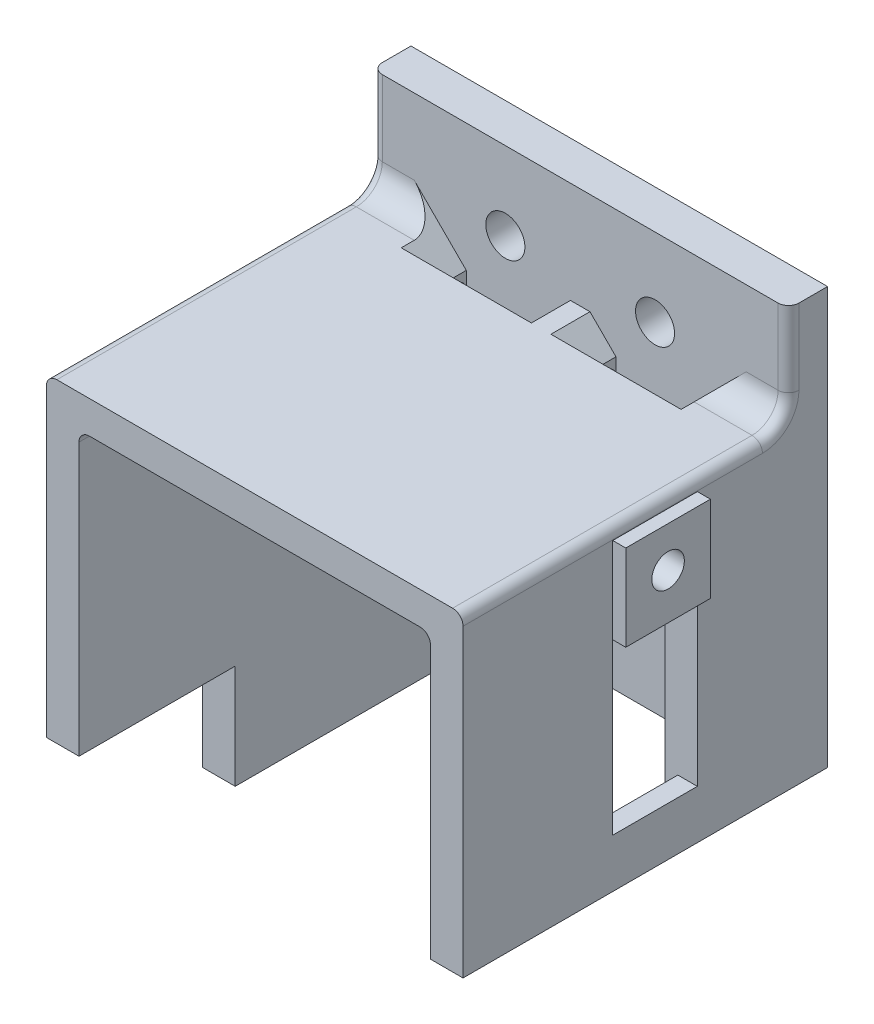
SolidWorks part; units mm, degrees
ref_plane "Płaszczyzna przednia" through (0, 0, 0) normal (0, 0, 1) x (1, 0, 0)
ref_plane "Płaszczyzna górna" through (0, 0, 0) normal (0, 1, 0) x (1, 0, 0)
ref_plane "Płaszczyzna prawa" through (0, 0, 0) normal (1, 0, 0) x (0, 0, -1)
sketch "Szkic1" plane through (0, 0, 0) normal (0, 0, 1) x (1, 0, 0)
  line L0 (-5.75, 3.4578) -> (5.75, 3.4578) construction
  line L2 (-16, 9.4578) -> (16, 9.4578)
  line L3 (-16, 9.4578) -> (-16, -2.5422)
  line L4 (-16, -2.5422) -> (16, -2.5422)
  line L5 (16, 9.4578) -> (16, -2.5422)
  line L6 (-16, 9.4578) -> (16, -2.5422) construction
  line L7 (-16, -2.5422) -> (16, 9.4578) construction
  circle A0 centre (-5.75, 3.4578) radius 1.5
  circle A1 centre (5.75, 3.4578) radius 1.5
  point P4 (0, 3.4578)
  point P10 (0, -2.5422)
  dimension "D1" = 3
  dimension "D2" = 3
  dimension "D3" = 5.75
  dimension "D4" = 5.75
  dimension "D5" = 32
  dimension "D6" = 6
extrude "Dodanie-wyciągnięcie1" add sketch "Szkic1" along normal blind 3
sketch "Szkic6" plane through (0, -2.5422, 0) normal (0, -1, 0) x (1, 0, 0)
  line L1 (-16, 3) -> (16, 3)
  line L2 (-16, 3) -> (-16, 0)
  line L3 (-16, 0) -> (16, 0)
  line L4 (16, 3) -> (16, 0)
extrude "Dodanie-wyciągnięcie3" add sketch "Szkic6" along normal blind 20
sketch "Szkic7" plane through (0, 0, 3) normal (0, 0, 1) x (1, 0, 0)
  line L0 (-16, 9.4578) -> (-16, -22.5422) construction
  line L1 (-16, -0.8422) -> (16, -0.8422)
  line L2 (-16, -0.8422) -> (-16, 1.6578)
  line L3 (-16, 1.6578) -> (16, 1.6578)
  line L4 (16, -0.8422) -> (16, 1.6578)
  line L5 (16, -22.5422) -> (16, 9.4578) construction
  line L6 (16, 9.4578) -> (-16, 9.4578) construction
  dimension "D1" = 2.5
  dimension "D2" = 10.3
extrude "Dodanie-wyciągnięcie4" add sketch "Szkic7" along normal blind 25
sketch "Szkic8" plane through (0, 0, 3) normal (0, 0, 1) x (1, 0, 0)
  line L0 (16, -22.5422) -> (-16, -22.5422) construction
  line L1 (-16, -0.8422) -> (-13.5, -0.8422)
  line L2 (-16, -0.8422) -> (-16, -22.5422)
  line L3 (-16, -22.5422) -> (-13.5, -22.5422)
  line L4 (-13.5, -0.8422) -> (-13.5, -22.5422)
  dimension "D1" = 2.5
extrude "Dodanie-wyciągnięcie5" add sketch "Szkic8" along normal up to surface (25 mm away) up to face at (0, 0.4078, 28)
sketch "Szkic9" plane through (0, 0, 3) normal (0, 0, 1) x (1, 0, 0)
  line L0 (16, -22.5422) -> (-13.5, -22.5422) construction
  line L1 (16, -0.8422) -> (13.5, -0.8422)
  line L2 (16, -0.8422) -> (16, -22.5422)
  line L3 (16, -22.5422) -> (13.5, -22.5422)
  line L4 (13.5, -0.8422) -> (13.5, -22.5422)
  dimension "D1" = 2.5
extrude "Dodanie-wyciągnięcie6" add sketch "Szkic9" along normal up to surface (25 mm away) up to face at (-4.5, -7.2422, 28)
sketch "Szkic10" plane through (-16, 0, 0) normal (-1, 0, 0) x (0, 0, 1)
  line L0 (3, 1.6578) -> (3, -12.8103) construction
  line L1 (28, 1.6578) -> (3, 1.6578) construction
  line L2 (3, -0.8422) -> (13, -0.8422)
  line L3 (3, -0.8422) -> (3, -10.8422)
  line L4 (3, -10.8422) -> (13, -10.8422)
  line L5 (13, -0.8422) -> (13, -10.8422)
  dimension "D1" = 10
  dimension "D2" = 10
  dimension "D3" = 2.5
extrude "Wytnij-wyciągnięcie1" cut sketch "Szkic10" against normal up to surface (2.5 mm away) up to face at (-13.5, -11.6922, 15.5)
sketch "Szkic11" plane through (0, 1.6578, 0) normal (0, 1, 0) x (1, 0, 0)
  line L0 (-16, -3) -> (16, -3) construction
  line L1 (-8.75, -3) -> (-2.75, -3)
  line L2 (-8.75, -3) -> (-8.75, -6)
  line L3 (-8.75, -6) -> (-2.75, -6)
  line L4 (-2.75, -3) -> (-2.75, -6)
  line L5 (16, -3) -> (-16, -3) construction
  line L6 (2.75, -3) -> (8.75, -3)
  line L7 (2.75, -3) -> (2.75, -6)
  line L8 (2.75, -6) -> (8.75, -6)
  line L9 (8.75, -3) -> (8.75, -6)
  dimension "D1" = 1.5
  dimension "D2" = 1.5
  dimension "D3" = 1.5
  dimension "D4" = 1.5
  dimension "D5" = 3
  dimension "D6" = 3
extrude "Wytnij-wyciągnięcie2" cut sketch "Szkic11" against normal up to surface (2.5 mm away) up to face at (-5.3333, -0.8422, 14.6667)
chamfer "Sfazowanie1" distance 2 angle 45 4 edges at (-8.75, 1.6578, 4.5) (2.75, 1.6578, 4.5) (8.75, 1.6578, 4.5) (-2.75, 1.6578, 4.5)
fillet "Zaokrąglenie1" radius 0.8 5 edges at (-13.5, -16.6922, 3) (-12.375, -0.8422, 3) (13.5, -11.6922, 3) (11.125, -0.8422, 3) (0, -0.8422, 3)
fillet "Zaokrąglenie2" radius 0.8 3 edges at (-14.35, -10.8422, 3) (-14.75, -10.8422, 13) (-14.75, -0.8422, 13)
fillet "Zaokrąglenie3" radius 2 2 edges at (13.375, 1.6578, 3) (-13.375, 1.6578, 3)
fillet "Zaokrąglenie4" radius 0.8 3 edges at (13.5, -0.8422, 15.9) (-13.5, -0.8422, 20.1) (13.2657, -1.0765, 3.2343)
fillet "Zaokrąglenie5" radius 0.8 6 edges at (16, 6.5578, 3) (16, 2.2436, 3.5858) (-16, 6.5578, 3) (-16, 2.2436, 3.5858) (16, 1.6578, 16.5) (-16, 1.6578, 16.5)
sketch "Szkic12" plane through (16, 0, 0) normal (1, 0, 0) x (0, 0, -1)
  line L0 (-28, -18.7922) -> (0, -18.7922) construction
  line L1 (-28, -22.5422) -> (-28, 0.8578) construction
  line L2 (0, -22.5422) -> (0, 9.4578) construction
  line L3 (0, -22.5422) -> (-28, -22.5422) construction
  line L4 (-10, -22.5422) -> (-10, 0.4779) construction
  line L6 (-10, -18.7922) -> (-16.5, -18.7922)
  line L7 (-10, -18.7922) -> (-10, -5.7922)
  line L8 (-10, -5.7922) -> (-16.5, -5.7922)
  line L9 (-16.5, -18.7922) -> (-16.5, -5.7922)
  dimension "D1" = 3.75
  dimension "D2" = 10
  dimension "D3" = 6.5
  dimension "D4" = 13
extrude "Wytnij-wyciągnięcie3" cut sketch "Szkic12" against normal up to surface (2.5 mm away) up to face at (13.5, -12.0922, 15.9)
sketch "Szkic13" plane through (16, 0, 0) normal (1, 0, 0) x (0, 0, -1)
  line L0 (-16.5, -12.2922) -> (-10, -12.2922) construction
  line L1 (-16.5, -5.7922) -> (-16.5, -18.7922) construction
  line L2 (-10, -18.7922) -> (-10, -5.7922) construction
  circle A0 centre (-13.25, -2.2922) radius 1.25
  dimension "D1" = 2.5
  dimension "D2" = 10
extrude "Wytnij-wyciągnięcie4" cut sketch "Szkic13" against normal blind 4
sketch "Szkic14" plane through (16, 0, 0) normal (1, 0, 0) x (0, 0, -1)
  line L0 (-10, -5.7922) -> (-10, 1.6015) construction
  line L2 (-16.5, -5.7922) -> (-10, -5.7922)
  line L3 (-16.5, -5.7922) -> (-16.5, 0.8124)
  line L4 (-16.5, 0.8124) -> (-10, 0.8124)
  line L5 (-10, -5.7922) -> (-10, 0.8124)
  circle A0 centre (-13.25, -2.2922) radius 1.25
extrude "Dodanie-wyciągnięcie7" add sketch "Szkic14" along normal blind 1
sketch "Szkic15" plane through (13.5, 0, 0) normal (-1, 0, 0) x (0, 0, 1)
  line L0 (16.5, -18.7922) -> (16.5, -22.5422) construction
  line L1 (28, -22.5422) -> (3.8, -22.5422) construction
  line L3 (10, -18.7922) -> (16.5, -18.7922)
  line L4 (10, -18.7922) -> (10, -22.5422)
  line L5 (10, -22.5422) -> (16.5, -22.5422)
  line L6 (16.5, -18.7922) -> (16.5, -22.5422)
extrude "Wytnij-wyciągnięcie5" cut sketch "Szkic15" against normal blind 1
sketch "Szkic16" plane through (0, -22.5422, 0) normal (0, -1, 0) x (1, 0, 0)
  line L0 (-13.5, 13) -> (-13.5, 28) construction
  line L1 (-16, 0) -> (-13.5, 0)
  line L2 (-16, 0) -> (-16, 16)
  line L3 (-16, 16) -> (-13.5, 16)
  line L4 (-13.5, 0) -> (-13.5, 16)
  dimension "D1" = 16
extrude "Dodanie-wyciągnięcie8" add sketch "Szkic16" along normal blind 8
sketch "Szkic17" plane through (-16, 0, 0) normal (-1, 0, 0) x (0, 0, 1)
  line L0 (16, -22.5422) -> (0, -22.5422) construction
  line L2 (0, -22.5422) -> (8, -22.5422)
  line L3 (0, -22.5422) -> (0, -20.5422)
  line L4 (0, -20.5422) -> (8, -20.5422)
  line L5 (8, -22.5422) -> (8, -20.5422)
  dimension "D1" = 2
  dimension "D2" = 8
extrude "Dodanie-wyciągnięcie9" add sketch "Szkic17" along normal blind 8
sketch "Szkic18" plane through (0, -22.5422, 0) normal (0, -1, 0) x (1, 0, 0)
  line L0 (-24, 0) -> (-16, 0) construction
  line L1 (-16, 16) -> (-16, 0) construction
  circle A0 centre (-20, 4) radius 1.75
  dimension "D3" = 3.5
  dimension "D1" = 4
  dimension "D2" = 4
extrude "Wytnij-wyciągnięcie6" cut sketch "Szkic18" against normal up to surface (2 mm away) up to face at (-20, -20.5422, 4)
